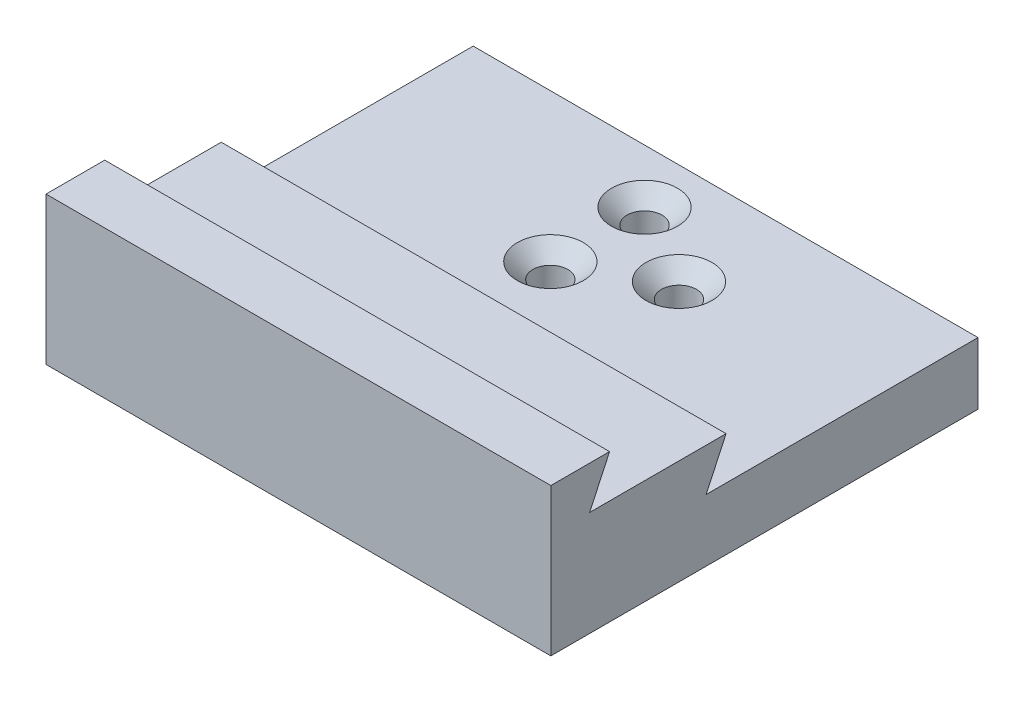
SolidWorks part; units mm, degrees
material "6061 Alloy"
ref_plane "Front Plane" through (0, 0, 0) normal (0, 0, 1) x (1, 0, 0)
ref_plane "Top Plane" through (0, 0, 0) normal (0, 1, 0) x (1, 0, 0)
ref_plane "Right Plane" through (0, 0, 0) normal (1, 0, 0) x (0, 0, -1)
sketch "Sketch1" plane through (0, 0, 0) normal (1, 0, 0) x (0, 0, -1)
  line L0 (0, 0) -> (0, 19)
  line L1 (0, 19) -> (7.5647, 19)
  line L2 (7.5647, 19) -> (5, 13.5)
  line L3 (5, 13.5) -> (22.5647, 13.5)
  line L4 (22.5647, 13.5) -> (20, 8)
  line L5 (20, 8) -> (55, 8)
  line L6 (55, 8) -> (55, 0)
  line L7 (55, 0) -> (0, 0)
  dimension "D1" = 65
  dimension "D2" = 65
  dimension "D3" = 5.5
  dimension "D4" = 5.5
  dimension "D5" = 8
  dimension "D6" = 35
  dimension "D7" = 50
  dimension "D8" = 5
extrude "Boss-Extrude1" add sketch "Sketch1" along normal blind 65
sketch "Sketch2" plane through (0, 0, -55) normal (0, 0, -1) x (-1, 0, 0)
  line L0 (-32.5, 8) -> (-32.5, 0) construction
  line L1 (-65, 8) -> (0, 8) construction
  line L2 (-65, 0) -> (0, 0) construction
  line L3 (-32.5, 4.5) -> (-12.5, 4.5) construction
  circle A0 centre (-12.5, 4.5) radius 2
  circle A1 centre (-52.5, 4.5) radius 2
  dimension "D1" = 4
  dimension "D3" = 3.5
  dimension "D2" = 20
extrude "M$_DRILL" cut sketch "Sketch2" against normal blind 20
sketch "Sketch3" plane through (0, 8, 0) normal (0, 1, 0) x (1, 0, 0)
  line L0 (0, 42) -> (65, 42) construction
  line L1 (0, 55) -> (0, 20) construction
  line L2 (65, 55) -> (65, 20) construction
  line L3 (65, 55) -> (0, 55) construction
  line L4 (32.5, 42) -> (32.5, 55) construction
  circle A0 centre (39.5, 42) radius 2.25
  circle A3 centre (29, 35.9378) radius 2.25
  circle A4 centre (29, 48.0622) radius 2.25
  point P18 (32.5, 42)
  dimension "D2" = 7
  dimension "D3" = 4.5
  dimension "D1" = 13
  dimension "D4" = 3
extrude "M4_through" cut sketch "Sketch3" against normal up to surface (8 mm away) up to face at (32.5, 0, -27.5)
chamfer "Chamfer1" distance 2 angle 45 3 edges at (39.5, 8, -39.75) (29, 8, -33.6878) (29, 8, -45.8122)
